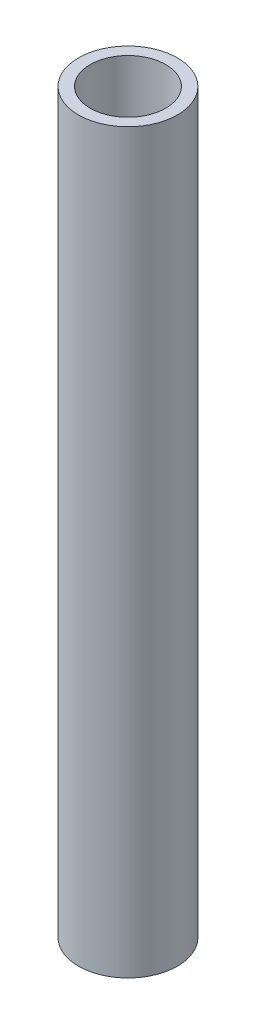
SolidWorks part; units mm, degrees
material "AISI 304"
ref_plane "Front Plane" through (0, 0, 0) normal (0, 0, 1) x (1, 0, 0)
ref_plane "Top Plane" through (0, 0, 0) normal (0, 1, 0) x (1, 0, 0)
ref_plane "Right Plane" through (0, 0, 0) normal (1, 0, 0) x (0, 0, -1)
ref_axis "Axial" through (0, 55, 0) along (0, -1, 0)
ref_plane "Bottom Plane" through (0, -12.065, 0) normal (0, 1, 0) x (1, 0, 0)
sketch "Sketch1" plane through (0, 0, 0) normal (0, 1, 0) x (1, 0, 0)
  circle A0 centre (0, 0) radius 0.4953
  circle A1 centre (0, 0) radius 0.6477
  dimension "D1" = 0.9906
  dimension "D2" = 1.2954
extrude "Needle" add sketch "Sketch1" against normal blind 9.652
